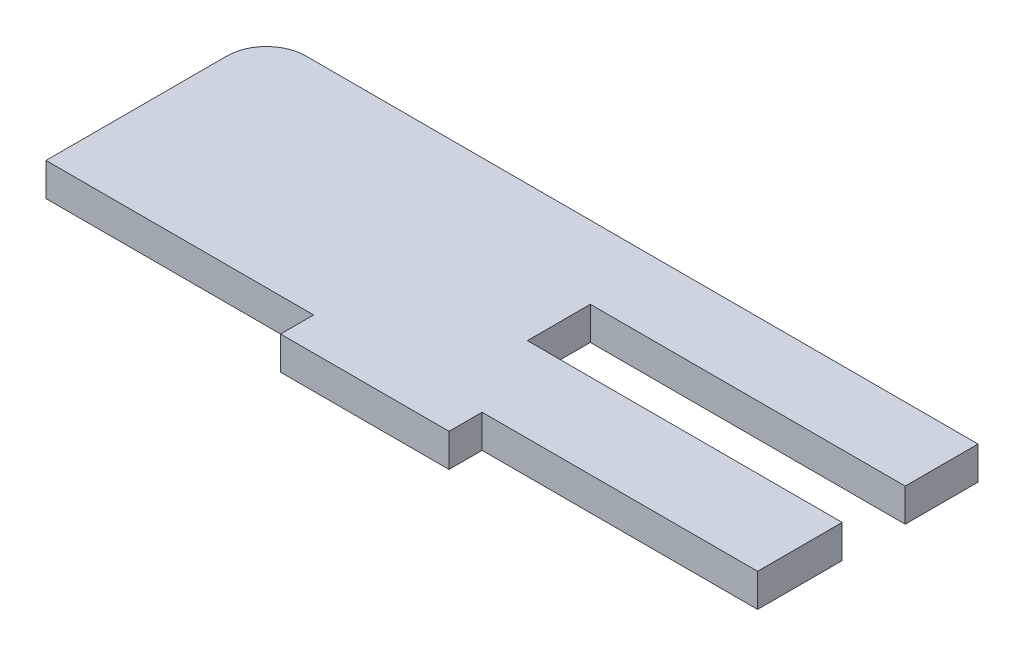
SolidWorks part; units mm, degrees
ref_plane "Front Plane" through (0, 0, 0) normal (0, 0, 1) x (1, 0, 0)
ref_plane "Top Plane" through (0, 0, 0) normal (0, 1, 0) x (1, 0, 0)
ref_plane "Right Plane" through (0, 0, 0) normal (1, 0, 0) x (0, 0, -1)
sketch "Sketch1" plane through (0, 0, 0) normal (0, 1, 0) x (1, 0, 0)
  line L1 (-431.0497, 194.9293) -> (-316.2417, 194.9293)
  line L2 (-431.0497, 194.9293) -> (-431.0497, 154.0353)
  line L3 (-431.0497, 154.0353) -> (-316.2417, 154.0353)
  line L4 (-316.2417, 194.9293) -> (-316.2417, 154.0353)
  dimension "D1" = 114.808
  dimension "D2" = 40.894
extrude "Boss-Extrude1" add sketch "Sketch1" along normal blind 5.334
fillet "Fillet1" radius 6.35 1 edges at (-431.0497, 2.667, -194.9293)
sketch "Sketch3" plane through (0, 5.334, 0) normal (0, 1, 0) x (1, 0, 0)
  line L0 (-431.0497, 154.0353) -> (-316.2417, 154.0353) construction
  line L1 (-387.8697, 159.3693) -> (-431.0497, 159.3693)
  line L2 (-387.8697, 159.3693) -> (-387.8697, 154.0353)
  line L3 (-387.8697, 154.0353) -> (-431.0497, 154.0353)
  line L4 (-431.0497, 159.3693) -> (-431.0497, 154.0353)
  line L5 (-360.6917, 159.3693) -> (-316.2417, 159.3693)
  line L6 (-360.6917, 159.3693) -> (-360.6917, 154.0353)
  line L7 (-360.6917, 154.0353) -> (-316.2417, 154.0353)
  line L8 (-316.2417, 159.3693) -> (-316.2417, 154.0353)
  line L9 (-387.8697, 159.3693) -> (-360.6917, 159.3693) construction
  dimension "D1" = 43.18
  dimension "D2" = 27.178
  dimension "D3" = 44.45
  dimension "D4" = 5.334
extrude "Cut-Extrude2" cut sketch "Sketch3" against normal through all
sketch "Sketch4" plane through (0, 0, 0) normal (0, -1, 0) x (-1, 0, 0)
  line L0 (316.2417, 159.3693) -> (316.2417, 194.9293) construction
  line L1 (316.2417, 183.1823) -> (367.0417, 183.1823)
  line L2 (316.2417, 183.1823) -> (316.2417, 173.0223)
  line L3 (316.2417, 173.0223) -> (367.0417, 173.0223)
  line L4 (367.0417, 183.1823) -> (367.0417, 173.0223)
  line L5 (387.8697, 154.0353) -> (360.6917, 154.0353) construction
  dimension "D1" = 18.9871
  dimension "D2" = 10.16
  dimension "D3" = 50.8
extrude "Cut-Extrude3" cut sketch "Sketch4" against normal through all
equation "\"MDF\"= .21in"
equation "\"Foamcore\"= .13in"
equation "\"Gmaterial\"= \"MDF\""
equation "\"D2@Sketch1\"=\"MDF\"+1.4"
equation "\"D1@Boss-Extrude1\"=\"MDF\""
equation "\"D4@Sketch3\"=\"MDF\""
